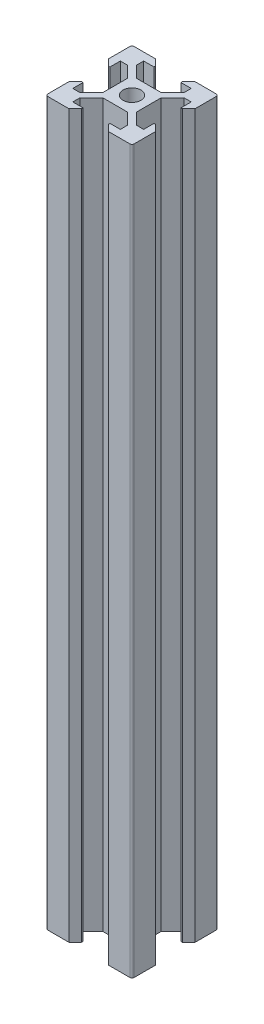
SolidWorks part; units mm, degrees
ref_plane "Front Plane" through (0, 0, 0) normal (0, 0, 1) x (1, 0, 0)
ref_plane "Top Plane" through (0, 0, 0) normal (0, 1, 0) x (1, 0, 0)
ref_plane "Right Plane" through (0, 0, 0) normal (1, 0, 0) x (0, 0, -1)
sketch "Sketch1" plane through (0, 0, 0) normal (0, 1, 0) x (1, 0, 0)
  line L0 (-2.1465, 12.2219) -> (22.938, 12.2219) construction
  line L1 (7.155, 13.9) -> (4.5, 16.555)
  line L2 (0.5, 0) -> (5.42, 0)
  line L3 (0, 0.5) -> (0, 5.42)
  line L4 (0.5, 20) -> (5.42, 20)
  line L5 (20, 0.5) -> (20, 19.5)
  line L6 (7.155, 13.9) -> (12.8341, 13.9)
  line L7 (6.1, 12.845) -> (6.1, 7.1491)
  line L8 (7.1445, 6.1) -> (12.8546, 6.1)
  line L9 (13.9, 12.8445) -> (13.9, 7.1491)
  line L10 (0, 20) -> (4.5, 20)
  line L11 (0, 20) -> (0, 15.5)
  line L12 (1.8, 15.5) -> (3.445, 15.5)
  line L13 (4.5, 18.2) -> (4.5, 16.555)
  line L14 (6.1, 12.845) -> (6.0943, 12.8393)
  line L15 (3.445, 15.5) -> (3.4393, 15.4943)
  line L16 (6.0943, 12.8393) -> (3.4393, 15.4943)
  line L17 (5.42, 20) -> (6.875, 18.545)
  line L18 (4.5, 20) -> (5.42, 20)
  line L19 (6.875, 20) -> (19.5, 20)
  line L20 (4.5, 18.2) -> (6.875, 18.2)
  line L21 (6.875, 20) -> (6.875, 18.2)
  line L22 (0, 14.58) -> (1.46, 13.12)
  line L23 (15.5, 18.2) -> (15.5, 16.555)
  line L24 (0, 15.5) -> (0, 13.12)
  line L25 (0, 13.12) -> (1.8, 13.12)
  line L26 (1.8, 15.5) -> (1.8, 13.12)
  line L27 (16.5507, 15.5) -> (18.2, 15.5)
  line L28 (15.5, 18.2) -> (13.12, 18.2)
  line L29 (13.12, 18.2) -> (13.12, 18.545)
  line L30 (13.12, 18.545) -> (14.575, 20)
  line L31 (18.2, 15.5) -> (18.2, 13.12)
  line L32 (18.2, 13.12) -> (18.5344, 13.12)
  line L33 (18.5344, 13.12) -> (20, 14.58)
  line L34 (12.8341, 13.9) -> (15.5, 16.555)
  line L35 (18.2, 4.5) -> (16.5585, 4.5)
  line L36 (16.5507, 15.5) -> (16.5585, 15.4922)
  line L37 (13.8926, 12.8372) -> (16.5585, 15.4922)
  line L38 (15.5, 3.4377) -> (15.5, 1.8)
  line L39 (18.2, 4.5) -> (18.2, 6.88)
  line L40 (18.2, 6.88) -> (18.6069, 6.88)
  line L41 (20, 5.42) -> (18.6069, 6.88)
  line L42 (15.5, 1.8) -> (13.12, 1.8)
  line L43 (13.12, 1.8) -> (13.12, 1.455)
  line L44 (14.575, 0) -> (13.12, 1.455)
  line L45 (13.9, 7.1491) -> (16.5585, 4.5)
  line L46 (12.8546, 6.1) -> (12.8412, 6.0865)
  line L47 (15.5, 3.4377) -> (15.4997, 3.4375)
  line L48 (12.8412, 6.0865) -> (15.4997, 3.4375)
  line L49 (1.8, 4.5) -> (3.4393, 4.5)
  line L50 (4.5, 3.4393) -> (4.5, 1.8)
  line L51 (1.46, 6.88) -> (1.8, 6.88)
  line L52 (1.8, 6.88) -> (1.8, 4.5)
  line L53 (0, 5.42) -> (1.46, 6.88)
  line L54 (4.5, 1.8) -> (6.875, 1.8)
  line L55 (6.875, 1.8) -> (6.875, 1.455)
  line L56 (5.42, 0) -> (6.875, 1.455)
  line L57 (3.4393, 4.5) -> (6.1, 7.1491)
  line L58 (14.575, 0) -> (19.5, 0)
  line L59 (7.1445, 6.1) -> (7.1583, 6.0861)
  line L60 (4.4977, 3.437) -> (7.1583, 6.0861)
  line L61 (0, 6.88) -> (0, 19.5)
  circle A0 centre (10, 10) radius 2.0746
  arc A1 (0.5, 0) -> (0, 0.5) centre (0.5, 0.5) cw
  arc A2 (19.5, 0) -> (20, 0.5) centre (19.5, 0.5) ccw
  arc A3 (19.5, 20) -> (20, 19.5) centre (19.5, 19.5) cw
  arc A4 (0, 19.5) -> (0.5, 20) centre (0.5, 19.5) cw
  point P22 (0, 0)
  point P25 (20, 0)
  dimension "D14" = 0.5
  dimension "D1" = 20
  dimension "D2" = 20
  dimension "D3" = 10
  dimension "D4" = 10
  dimension "D5" = 7.8
  dimension "D6" = 7.8
  dimension "D7" = 3.9
  dimension "D8" = 3.9
  dimension "D9" = 4.5
  dimension "D10" = 4.5
  dimension "D11" = 45
  dimension "D12" = 1.5
  dimension "D13" = 1.5
  dimension "D15" = 2.375
  dimension "D16" = 1.8
  dimension "D17" = 9.155
  dimension "D18" = 45
  dimension "D19" = 2.38
  dimension "D20" = 1.8
  dimension "D21" = 4.58
  dimension "D22" = 45
  dimension "D24" = 2.38
  dimension "D25" = 2.38
  dimension "D27" = 2.38
  dimension "D28" = 9.16
  dimension "D29" = 4.58
  dimension "D30" = 2.38
  dimension "D31" = 1.8
  dimension "D32" = 45
  dimension "D33" = 1.5
  dimension "D34" = 2.38
  dimension "D35" = 45
  dimension "D36" = 4.58
  dimension "D37" = 2.375
  dimension "D39" = 45
  dimension "D40" = 4.58
  dimension "D41" = 1.5
extrude "Boss-Extrude2" add sketch "Sketch1" along normal blind 1000 contours L7 L0 L9 L37 L36 L27 L31 L32 L33 L5 A3 L19 L30 L29 L28 L23 L34 L6 L1 L13 L20 L21 L17 L4 A4 L11 L24 L22 L25 L26 L12 L15 L16 L14 | L0 L7 L57 L49 L52 L51 L53 L3 A1 L2 L56 L55 L54 L50 L60 L59 L8 L46 L48 L47 L38 L42 L43 L44 L58 A2 L5 L41 L40 L39 L35 L45 L9 A0 region at (6.3146, 0, -12.5334) region at (10, 0, -12.1984)
ref_axis "Eje1" through (10, 171.227, -10) along (0, -1, 0)
ref_plane "Plano1" through (0, 0, -10) normal (0, 0, -1) x (-1, 0, 0)
sketch "Croquis1" plane through (0, 1000, 0) normal (0, 1, 0) x (1, 0, 0)
  line L1 (20.9803, -1.3406) -> (-0.9803, -1.3406)
  line L2 (20.9803, -1.3406) -> (20.9803, 21.3406)
  line L3 (20.9803, 21.3406) -> (-0.9803, 21.3406)
  line L4 (-0.9803, -1.3406) -> (-0.9803, 21.3406)
  line L5 (20.9803, -1.3406) -> (-0.9803, 21.3406) construction
  line L6 (20.9803, 21.3406) -> (-0.9803, -1.3406) construction
  point P0 (10, 10)
extrude "Cortar-Extruir1" cut sketch "Croquis1" against normal blind 833
ref_plane "Plano2" through (0, 83.5, 0) normal (0, 1, 0) x (1, 0, 0)
